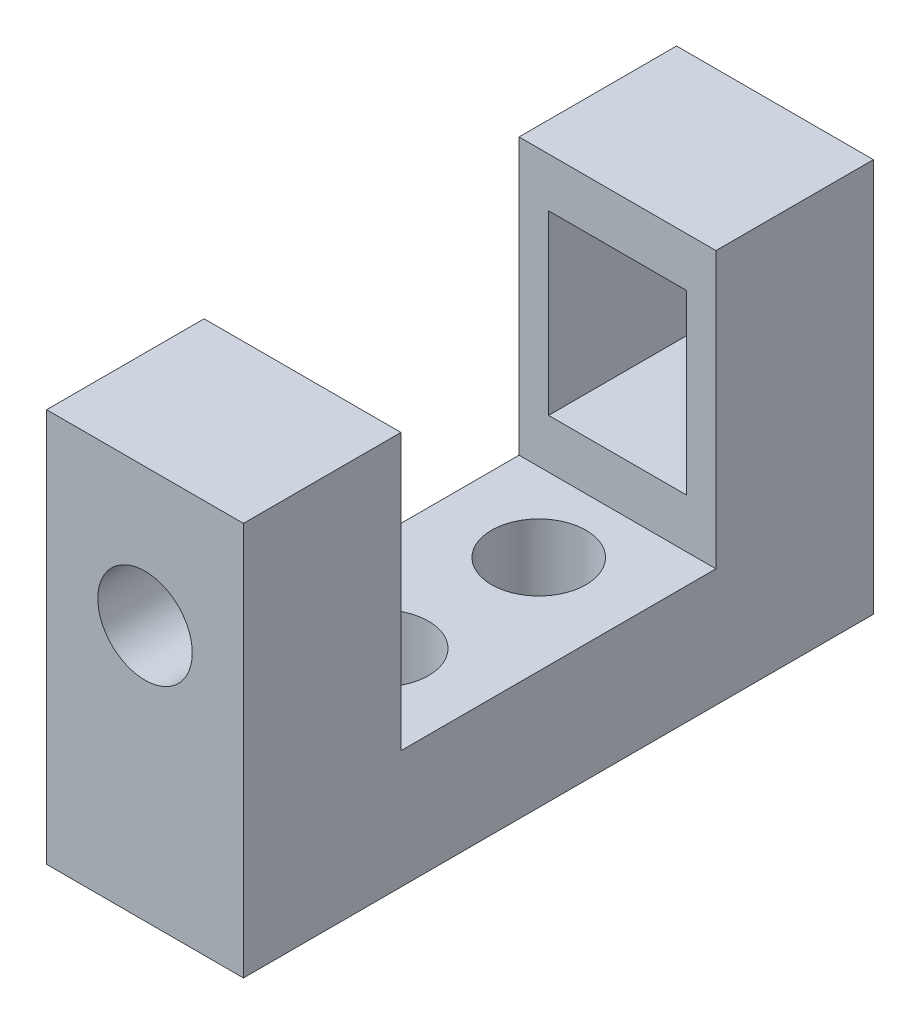
SolidWorks part; units mm, degrees
ref_plane "Front Plane" through (0, 0, 0) normal (0, 0, 1) x (1, 0, 0)
ref_plane "Top Plane" through (0, 0, 0) normal (0, 1, 0) x (1, 0, 0)
ref_plane "Right Plane" through (0, 0, 0) normal (1, 0, 0) x (0, 0, -1)
sketch "Sketch1" plane through (0, 0, 0) normal (0, 0, 1) x (1, 0, 0)
  line L1 (-2.5, 3.5) -> (2.5, 3.5)
  line L2 (-2.5, 3.5) -> (-2.5, -3.5)
  line L3 (-2.5, -3.5) -> (2.5, -3.5)
  line L4 (2.5, 3.5) -> (2.5, -3.5)
  line L5 (-2.5, 3.5) -> (2.5, -3.5) construction
  line L6 (-2.5, -3.5) -> (2.5, 3.5) construction
  point P0 (0, 0)
  dimension "D1" = 7
  dimension "D2" = 5
extrude "Boss-Extrude1" add sketch "Sketch1" along normal mid plane 4
sketch "Sketch9" plane through (0, -3.5, 0) normal (0, -1, 0) x (1, 0, 0)
  line L5 (2.5, 2) -> (6.5, 2)
  line L7 (2.5, -2) -> (6.5, -2)
  line L8 (6.5, 2) -> (6.5, -2)
  line L9 (-2.5, -2) -> (2.5, -2) construction
  line L10 (-2.5, -2) -> (2.5, -2)
  line L12 (-2.5, 2) -> (-2.5, -2) construction
  line L14 (2.5, 2) -> (2.5, 14)
  line L15 (2.5, 14) -> (-2.5, 14)
  line L16 (-2.5, 2) -> (-2.5, 14)
  line L17 (-2.5, -2) -> (-2.5, 2)
  dimension "D1" = 12
  dimension "D2" = 4
extrude "Boss-Extrude3" add sketch "Sketch9" along normal blind 3
sketch "Sketch10" plane through (0, -3.5, 0) normal (0, 1, 0) x (1, 0, 0)
  line L0 (-2.5, -2) -> (2.5, -2) construction
  line L3 (2.5, 2) -> (6.5, 2) construction
  point P1 (4.5, 0)
  point P2 (0, -4)
  point P4 (0, -8)
  point P13 (4.5, 2)
  dimension "D1" = 2
  dimension "D2" = 6
sketch "Sketch13" plane through (0, -3.5, 0) normal (0, 1, 0) x (1, 0, 0)
  line L0 (-2.5, -14) -> (-2.5, -2) construction
  line L1 (2.5, -14) -> (-2.5, -14)
  line L2 (2.5, -14) -> (2.5, -10)
  line L3 (2.5, -10) -> (-2.5, -10)
  line L4 (-2.5, -14) -> (-2.5, -10)
  dimension "D1" = 4
extrude "Boss-Extrude4" add sketch "Sketch13" along normal blind 7
sketch "Sketch14" plane through (0, -3.5, 0) normal (0, 1, 0) x (1, 0, 0)
  line L0 (-2.5, -14) -> (2.5, -14) construction
  line L1 (2.5, -10) -> (6.5, -10)
  line L2 (2.5, -10) -> (2.5, -14)
  line L3 (2.5, -14) -> (6.5, -14)
  line L4 (6.5, -10) -> (6.5, -14)
  line L5 (6.5, -2) -> (2.5, -2) construction
extrude "Boss-Extrude6" add sketch "Sketch14" against normal up to surface (3 mm away) up to face at (2.1667, -6.5, 4.6667)
fillet "Fillet1" radius 2.5 2 edges at (2.5, -5, 2) (2.5, -5, 10)
sketch "Sketch15" plane through (0, 0, -2) normal (0, 0, -1) x (-1, 0, 0)
  line L0 (-1.75, 2.25) -> (-1.75, -2.25)
  line L5 (-1.5, 2) -> (-1.5, -2) construction
  line L6 (1.5, -2) -> (-1.5, -2) construction
  line L7 (1.5, 2) -> (-1.5, 2) construction
  line L8 (1.5, 2) -> (1.5, -2) construction
  line L9 (-1.5, 2) -> (-1.5, -2) construction
  line L10 (1.5, -2) -> (-1.5, -2) construction
  line L11 (1.5, 2) -> (-1.5, 2) construction
  line L12 (1.5, 2) -> (1.5, -2) construction
  line L13 (1.75, -2.25) -> (-1.75, -2.25)
  line L14 (1.75, 2.25) -> (1.75, -2.25)
  line L15 (1.75, 2.25) -> (-1.75, 2.25)
  dimension "D1" = 0.25
sketch "Sketch16" plane through (0, 0, 14) normal (0, 0, 1) x (1, 0, 0)
  point P0 (0, 0)
hole_wizard "M2 Clearance Hole3" positions "Sketch17" profile "Sketch18" hole size "M2" standard "ISO"
sketch "Sketch17" plane through (0, 0, 14) normal (0, 0, 1) x (1, 0, 0)
  point P0 (0, 0)
sketch "Sketch18" plane through (0, 0, 14) normal (1, 0, 0) x (0, -1, 0)
  line L0 (0, 0) -> (0, 4.72)
  line L1 (0, 4.72) -> (1.2, 3.999)
  line L2 (1.2, 3.999) -> (1.2, 0)
  line L5 (1.2, 0) -> (0, 0)
  line L10 (0, 4.72) -> (-1.2, 3.999) construction
  line L11 (0, -6.35) -> (0, 107.95) construction
  dimension "Hole Dia." = 2.4
  dimension "Hole Depth" = 3.999
  dimension "Drill Angle" = 118
extrude "Cut-Extrude1" cut sketch "Sketch15" against normal up to surface (4 mm away) up to face at (0, 0, 2)
sketch "Sketch19" plane through (0, -3.5, 0) normal (0, 1, 0) x (1, 0, 0)
  line L0 (6.5, -14) -> (6.5, -10) construction
  point P0 (4.5, -12)
  point P4 (6.5, -12)
hole_wizard "M2 Clearance Hole2" positions "Sketch20" profile "Sketch21" hole size "M2" standard "ISO"
sketch "Sketch20" plane through (0, -3.5, 0) normal (0, 1, 0) x (1, 0, 0)
  point P0 (4.5, -12)
  point P3 (0, -8)
  point P6 (0, -4)
  point P9 (4.5, 0)
sketch "Sketch21" plane through (4.5, -3.5, 12) normal (1, 0, 0) x (0, 0, 1)
  line L0 (0, 0) -> (0, 4.721)
  line L1 (0, 4.721) -> (1.2, 4)
  line L2 (1.2, 4) -> (1.2, 0)
  line L5 (1.2, 0) -> (0, 0)
  line L10 (0, 4.721) -> (-1.2, 4) construction
  line L11 (0, -6.35) -> (0, 107.95) construction
  dimension "Hole Dia." = 2.4
  dimension "Hole Depth" = 4
  dimension "Drill Angle" = 118
sketch "Sketch22" plane through (0, -3.5, 0) normal (0, 1, 0) x (1, 0, 0)
  line L0 (2.5, 2) -> (6.5, 2) construction
  line L1 (2.5, -14) -> (6.5, -14)
  line L2 (2.5, -14) -> (2.5, 2)
  line L3 (2.5, 2) -> (6.5, 2)
  line L4 (6.5, -14) -> (6.5, 2)
  line L5 (6.5, -14) -> (6.5, -10) construction
extrude "Cut-Extrude2" cut sketch "Sketch22" against normal up to surface (3 mm away) up to face at (4.5, -6.5, 10.8)
